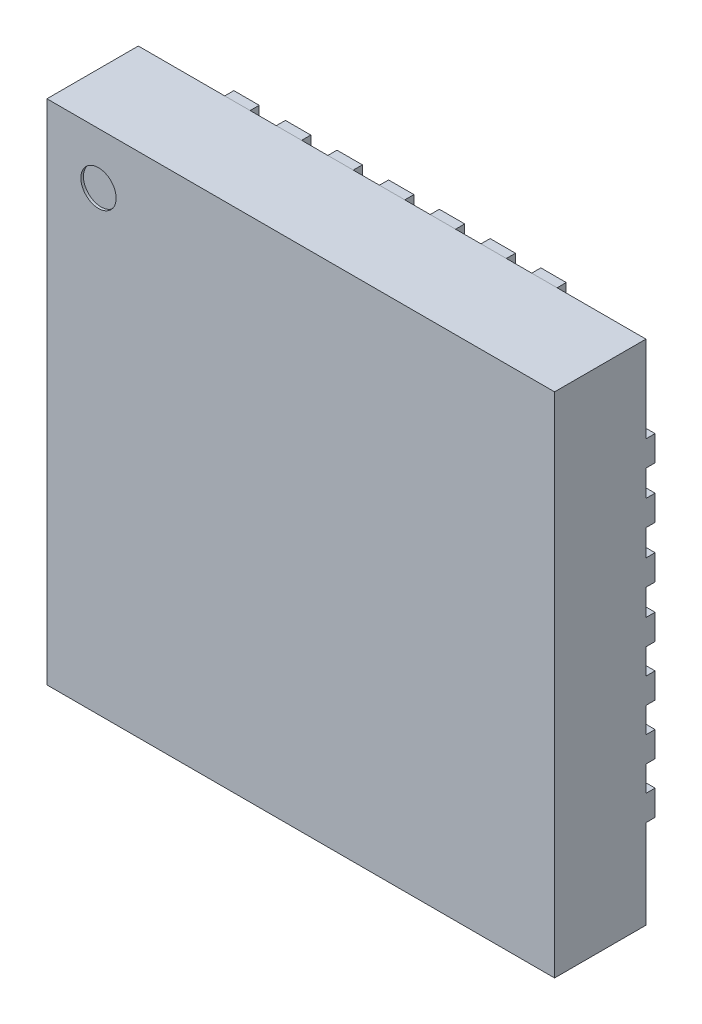
SolidWorks part; units mm, degrees
ref_plane "Front Plane" through (0, 0, 0) normal (0, 0, 1) x (1, 0, 0)
ref_plane "Top Plane" through (0, 0, 0) normal (0, 1, 0) x (1, 0, 0)
ref_plane "Right Plane" through (0, 0, 0) normal (1, 0, 0) x (0, 0, -1)
sketch "Sketch1" plane through (0, 0, 0) normal (0, 0, 1) x (1, 0, 0)
  line L1 (0, 0) -> (5, 0)
  line L2 (0, 0) -> (0, 5)
  line L3 (0, 5) -> (5, 5)
  line L4 (5, 0) -> (5, 5)
  dimension "D1" = 5
  dimension "D2" = 5
extrude "Boss-Extrude1" add sketch "Sketch1" along normal blind 0.9
sketch "Sketch2" plane through (0, 0, 0) normal (0, 0, -1) x (-1, 0, 0)
  line L0 (-2.5, 5) -> (-2.5, 0) construction
  line L1 (-5, 5) -> (0, 5) construction
  line L2 (0, 0) -> (-5, 0) construction
  line L3 (-2.117, 5) -> (-1.867, 5)
  line L4 (-2.625, 5) -> (-2.375, 5)
  line L5 (-2.625, 5) -> (-2.625, 4.395)
  line L6 (-2.117, 5) -> (-2.117, 4.395)
  line L7 (-2.375, 5) -> (-2.375, 4.395)
  line L8 (-1.867, 5) -> (-1.867, 4.395)
  line L9 (-1.609, 5) -> (-1.359, 5)
  line L10 (-1.609, 5) -> (-1.609, 4.395)
  line L11 (-1.359, 5) -> (-1.359, 4.395)
  line L12 (-1.101, 5) -> (-0.851, 5)
  line L13 (-1.101, 5) -> (-1.101, 4.395)
  line L14 (-0.851, 5) -> (-0.851, 4.395)
  line L15 (-3.125, 5) -> (-2.875, 5)
  line L16 (-3.125, 5) -> (-3.125, 4.395)
  line L17 (-2.875, 5) -> (-2.875, 4.395)
  line L18 (-3.625, 5) -> (-3.375, 5)
  line L19 (-3.625, 5) -> (-3.625, 4.395)
  line L20 (-3.375, 5) -> (-3.375, 4.395)
  line L21 (-4.125, 5) -> (-3.875, 5)
  line L22 (-4.125, 5) -> (-4.125, 4.395)
  line L23 (-3.875, 5) -> (-3.875, 4.395)
  arc A0 (-2.625, 4.395) -> (-2.375, 4.395) centre (-2.5, 4.395) ccw
  arc A1 (-2.117, 4.395) -> (-1.867, 4.395) centre (-1.992, 4.395) ccw
  arc A2 (-1.609, 4.395) -> (-1.359, 4.395) centre (-1.484, 4.395) ccw
  arc A3 (-1.101, 4.395) -> (-0.851, 4.395) centre (-0.976, 4.395) ccw
  arc A4 (-3.125, 4.395) -> (-2.875, 4.395) centre (-3, 4.395) ccw
  arc A5 (-3.625, 4.395) -> (-3.375, 4.395) centre (-3.5, 4.395) ccw
  arc A6 (-4.125, 4.395) -> (-3.875, 4.395) centre (-4, 4.395) ccw
  point P10 (-2.5, 5)
  dimension "D2" = 0.605
  dimension "D3" = 0.125
  dimension "D1" = 0.25
  dimension "D4" = 4
  dimension "D5" = 4
extrude "Boss-Extrude3" add sketch "Sketch2" along normal blind 0.09 separate body
ref_plane "Plane1" through (0, 0, 0) normal (0.7071, -0.7071, 0) x (-0.7071, -0.7071, 0)
ref_plane "Plane2" through (2.5, 2.5, 0) normal (-0.7071, -0.7071, 0) x (-0.7071, 0.7071, 0)
ref_axis "Axis1" through (2.5, 2.5, 0.945) along (0, 0, -1)
pattern_circular "CirPattern1" count 4 over 360 about axis through (2.5, 2.5, 0.945) along (0, 0, -1) of "Boss-Extrude3"
sketch "Sketch4" plane through (0, 0, 0.9) normal (0, 0, 1) x (1, 0, 0)
  line L0 (5, 5) -> (0, 5) construction
  line L1 (0, 5) -> (0, 0) construction
  circle A0 centre (0.508, 4.492) radius 0.1737
  dimension "D1" = 0.508
  dimension "D2" = 0.508
extrude "Cut-Extrude1" cut sketch "Sketch4" against normal blind 0.0254
sketch "Sketch5" plane through (0, 0, 0) normal (0, 0, -1) x (-1, 0, 0)
  line L0 (-2.5, 5) -> (-2.5, 0) construction
  line L1 (-2.375, 5) -> (-2.625, 5) construction
  line L2 (-2.625, 0) -> (-2.375, 0) construction
  line L3 (-1.306, 4.075) -> (-0.925, 4.075) construction
  line L4 (-5, 2.625) -> (-5, 2.375) construction
  line L5 (-5, 2.5) -> (0, 2.5) construction
  line L6 (0, 2.375) -> (0, 2.625) construction
  line L7 (-4.075, 4.075) -> (-1.306, 4.075)
  line L8 (-4.075, 4.075) -> (-4.075, 0.925)
  line L9 (-4.075, 0.925) -> (-0.925, 0.925)
  line L10 (-0.925, 3.694) -> (-0.925, 0.925)
  line L11 (-0.925, 4.075) -> (-0.925, 3.694) construction
  arc A0 (-1.306, 4.075) -> (-0.925, 3.694) centre (-0.925, 4.075) ccw
  point P17 (-4.075, 2.5)
  point P18 (-2.5, 0.925)
  dimension "D3" = 0.381
  dimension "D1" = 3.15
  dimension "D2" = 3.15
extrude "Boss-Extrude5" add sketch "Sketch5" along normal blind 0.09
